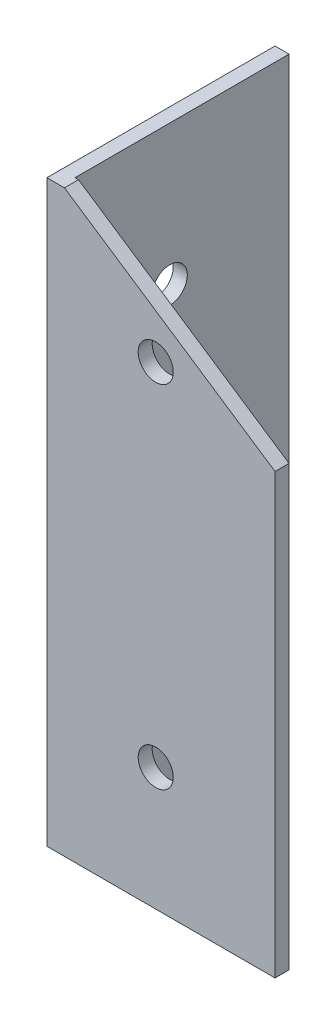
SolidWorks part; units mm, degrees
ref_plane "Спереди" through (0, 0, 0) normal (0, 0, 1) x (1, 0, 0)
ref_plane "Сверху" through (0, 0, 0) normal (0, 1, 0) x (1, 0, 0)
ref_plane "Справа" through (0, 0, 0) normal (1, 0, 0) x (0, 0, -1)
sketch "Эскиз1" plane through (0, 0, 0) normal (0, 1, 0) x (1, 0, 0)
  line L0 (0, 0) -> (65, 0)
  line L1 (0, 0) -> (0, 65)
extrude "Вытянуть-Тонкостенный1" add sketch "Эскиз1" along normal blind 165 thin thin type one direction wall 4
sketch "Эскиз2" plane through (0, 0, 0) normal (0, 0, 1) x (1, 0, 0)
  circle A0 centre (31, 235) radius 5
  circle A1 centre (31, 135) radius 5
  circle A2 centre (31, 35) radius 5
  dimension "D1" = 3
extrude "Вырез-Вытянуть1" cut sketch "Эскиз2" against normal blind 10
sketch "Эскиз3" plane through (0, 0, 0) normal (-1, 0, 0) x (0, 0, 1)
  circle A0 centre (-31, 225) radius 5
  circle A1 centre (-31, 125) radius 5
  circle A2 centre (-31, 25) radius 5
  dimension "D1" = 3
extrude "Вырез-Вытянуть2" cut sketch "Эскиз3" against normal blind 10
sketch "Эскиз4" plane through (0, 0, 0) normal (0, 0, 1) x (1, 0, 0)
  line L0 (5, 165) -> (65, 125)
  line L1 (65, 165) -> (65, 0) construction
  line L2 (65, 165) -> (0, 165) construction
  line L3 (65, 125) -> (65, 165)
  line L4 (65, 165) -> (5, 165)
  point P2 (65, 141.0753)
  point P5 (1.916, 186.0143)
  point P6 (65, 185)
extrude "Вырез-Вытянуть3" cut sketch "Эскиз4" against normal through all
